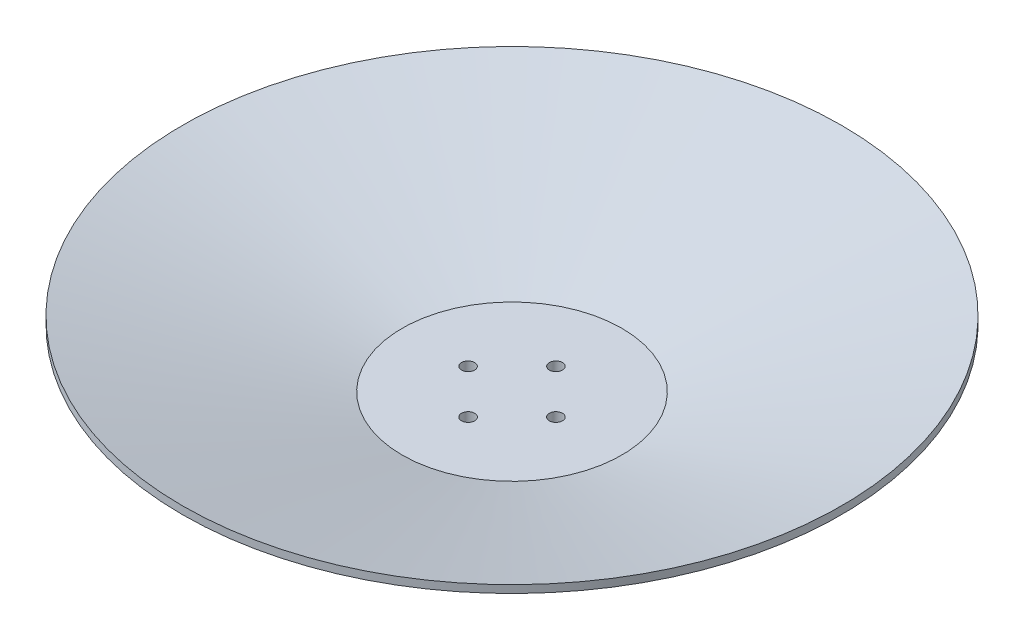
SolidWorks part; units mm, degrees
ref_plane "Front Plane" through (0, 0, 0) normal (0, 0, 1) x (1, 0, 0)
ref_plane "Top Plane" through (0, 0, 0) normal (0, 1, 0) x (1, 0, 0)
ref_plane "Right Plane" through (0, 0, 0) normal (1, 0, 0) x (0, 0, -1)
sketch "Sketch2" plane through (0, 0, 0) normal (0, 0, 1) x (1, 0, 0)
  line L0 (0, 0) -> (35, 0)
  line L4 (0, 7.2266) -> (0, 0)
  line L5 (0, 7.2266) -> (0, 20)
  line L8 (150, 46.5) -> (43.2341, 9.4894)
  line L9 (0, 20) -> (50, 20)
  line L10 (50, 20) -> (150, 50)
  line L12 (150, 46.5) -> (150, 50)
  line L13 (43.2341, 9.4894) -> (35, 0)
  point P3 (146.894, 79.8794)
  point P4 (146.9072, 81.3362)
  point P10 (150, 85.1073)
  point P12 (146.9247, 82.6668)
  point P13 (151.9173, 75.8742)
  point P14 (150, 51.6339)
  point P15 (68.65, 20.1355)
  point P16 (0, 0)
  dimension "D1" = 35
  dimension "D2" = 3.5
  dimension "D3" = 50
  dimension "D4" = 20
  dimension "D5" = 150
  dimension "D6" = 12.5
  dimension "D7" = 50
revolve "Revolve1" add sketch "Sketch2" angle 360 about L5
sketch "Sketch3" plane through (0, 0, 0) normal (0, -1, 0) x (1, 0, 0)
  circle A0 centre (0, 20) radius 3
  circle A1 centre (20, 0) radius 3
  circle A2 centre (0, -20) radius 3
  circle A3 centre (-20, 0) radius 3
  point P12 (0, 0)
  dimension "D1" = 20
  dimension "D2" = 4
extrude "Cut-Extrude1" cut sketch "Sketch3" against normal through all
